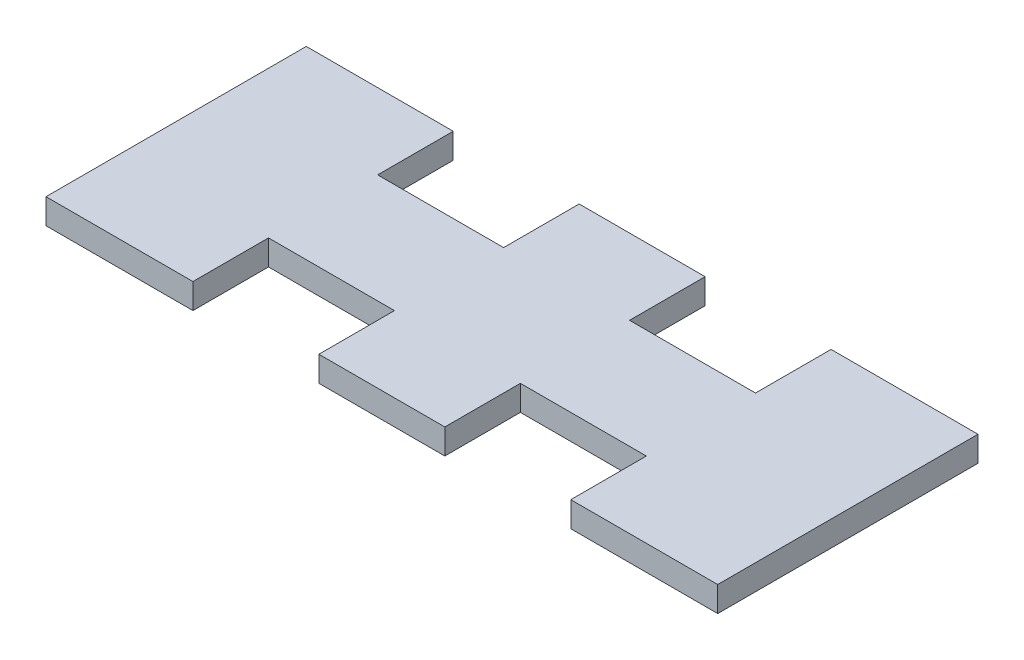
SolidWorks part; units mm, degrees
ref_plane "Alzado" through (0, 0, 0) normal (0, 0, 1) x (1, 0, 0)
ref_plane "Planta" through (0, 0, 0) normal (0, 1, 0) x (1, 0, 0)
ref_plane "Vista lateral" through (0, 0, 0) normal (1, 0, 0) x (0, 0, -1)
sketch "Croquis1" plane through (0, 0, 0) normal (0, 1, 0) x (1, 0, 0)
  line L0 (0, 0) -> (17.5, 0)
  line L1 (17.5, 0) -> (17.5, 9)
  line L2 (17.5, 9) -> (32.5, 9)
  line L3 (32.5, 9) -> (32.5, 0)
  line L4 (32.5, 0) -> (47.5, 0)
  line L5 (0, 0) -> (0, 31)
  line L6 (47.5, 9) -> (47.5, 0)
  line L7 (62.5, 9) -> (47.5, 9)
  line L8 (62.5, 0) -> (62.5, 9)
  line L9 (80, 0) -> (62.5, 0)
  line L10 (0, 31) -> (17.5, 31)
  line L11 (17.5, 31) -> (17.5, 22)
  line L12 (17.5, 22) -> (32.5, 22)
  line L13 (32.5, 22) -> (32.5, 31)
  line L14 (32.5, 31) -> (47.5, 31)
  line L15 (47.5, 31) -> (47.5, 22)
  line L16 (47.5, 22) -> (62.5, 22)
  line L17 (62.5, 22) -> (62.5, 31)
  line L18 (62.5, 31) -> (80, 31)
  line L19 (80, 31) -> (80, 0)
  dimension "D1" = 17.5
  dimension "D2" = 9
  dimension "D3" = 15
  dimension "D4" = 31
  dimension "D5" = 9
  dimension "D6" = 9
  dimension "D7" = 9
  dimension "D8" = 9
  dimension "D9" = 9
  dimension "D10" = 9
extrude "Saliente-Extruir1" add sketch "Croquis1" along normal blind 3
